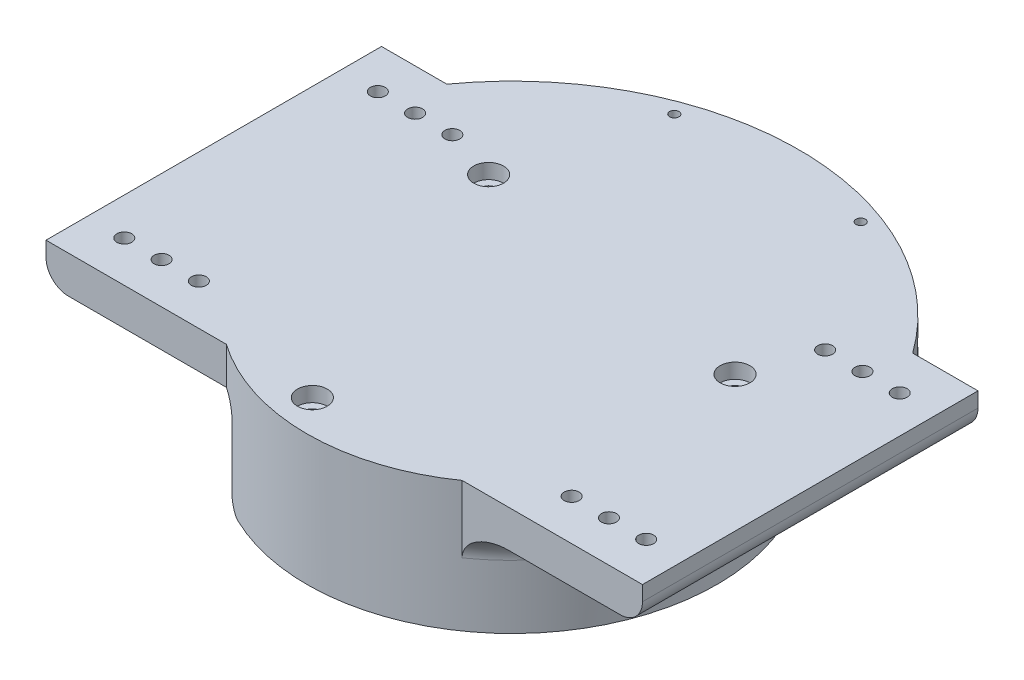
SolidWorks part; units mm, degrees
material "6061 合金"
ref_plane "前视基准面" through (0, 0, 0) normal (0, 0, 1) x (1, 0, 0)
ref_plane "上视基准面" through (0, 0, 0) normal (0, 1, 0) x (1, 0, 0)
ref_plane "右视基准面" through (0, 0, 0) normal (1, 0, 0) x (0, 0, -1)
sketch "草图1" plane through (0, 0, 0) normal (0, 1, 0) x (1, 0, 0)
  line L0 (-80, 0) -> (80, 0) construction
  line L1 (-80, 45) -> (-62.482, 45)
  line L2 (-80, 45) -> (-80, -45)
  line L3 (-80, -45) -> (-31.6228, -45)
  line L4 (80, 45) -> (80, -45)
  line L5 (-80, 45) -> (80, -45) construction
  line L6 (-80, -45) -> (80, 45) construction
  line L7 (62.482, 45) -> (80, 45)
  line L8 (43.5634, 16.2627) -> (0, 0) construction
  line L9 (-55, 0) -> (0, 0) construction
  line L10 (31.6228, -45) -> (80, -45)
  circle A5 centre (0, 0) radius 46.5 construction
  circle A9 centre (43.5634, 16.2627) radius 2
  circle A10 centre (-7.6978, -45.8584) radius 2
  circle A11 centre (-35.8657, 29.5957) radius 2
  arc A14 (-31.6228, -45) -> (31.6228, -45) centre (0, 0) ccw
  circle A15 centre (0, 0) radius 77 construction
  arc A16 (62.482, 45) -> (-62.482, 45) centre (0, 0) ccw
  dimension "D5" = 154
  dimension "D8" = 93
  dimension "D9" = 4
  dimension "D11" = 3
  dimension "D2" = 160
  dimension "D3" = 45
  dimension "D10" = 20.471
extrude "凸台-拉伸3" add sketch "草图1" along normal blind 10
sketch "草图4" plane through (0, 0, 0) normal (0, 1, 0) x (1, 0, 0)
  line L0 (-125, 0) -> (125, 0) construction
  line L5 (-125, 65) -> (125, -65) construction
  line L6 (-125, -65) -> (125, 65) construction
  line L7 (0, 0) -> (-27.5, -47.6314) construction
  line L8 (43.5634, 16.2627) -> (0, 0) construction
  line L9 (-55, 0) -> (0, 0) construction
  line L10 (-27.5, -47.6314) -> (-25, -43.3013)
  line L11 (-55, 0) -> (-50, 0)
  arc A0 (-25, -43.3013) -> (-50, 0) centre (0, 0) ccw
  circle A5 centre (0, 0) radius 46.5 construction
  arc A12 (-27.5, -47.6314) -> (-55, 0) centre (0, 0) ccw
  dimension "D1" = 100
  dimension "D4" = 110
  dimension "D5" = 60
  dimension "D8" = 93
  dimension "D10" = 20.471
extrude "凸台-拉伸4" add sketch "草图4" against normal blind 25
sketch "草图6" plane through (0, 10, 0) normal (0, 1, 0) x (1, 0, 0)
  line L0 (70, 34) -> (60, 34) construction
  line L1 (-70, 34) -> (70, 34) construction
  line L2 (-70, 34) -> (-70, -34) construction
  line L3 (-70, -34) -> (70, -34) construction
  line L4 (70, 34) -> (70, -34) construction
  line L5 (-70, 34) -> (70, -34) construction
  line L6 (-70, -34) -> (70, 34) construction
  line L7 (-70, 34) -> (-60, 34) construction
  circle A0 centre (70, -34) radius 2
  circle A1 centre (70, 34) radius 2
  circle A2 centre (60, 34) radius 2
  circle A3 centre (60, -34) radius 2
  circle A4 centre (50, 34) radius 2
  circle A5 centre (50, -34) radius 2
  circle A6 centre (-70, -34) radius 2
  circle A7 centre (-70, 34) radius 2
  circle A8 centre (-60, 34) radius 2
  circle A9 centre (-60, -34) radius 2
  circle A10 centre (-50, 34) radius 2
  circle A11 centre (-50, -34) radius 2
  point P0 (0, 0)
  dimension "D3" = 4
  dimension "D4" = 4
  dimension "D5" = 3
  dimension "D7" = 4
  dimension "D8" = 4
  dimension "D9" = 3
  dimension "D1" = 68
  dimension "D2" = 140
  dimension "D6" = 10
  dimension "D10" = 10
extrude "切除-拉伸1" cut sketch "草图6" against normal up to next
sketch "草图7" plane through (0, 10, 0) normal (0, 1, 0) x (1, 0, 0)
  circle A1 centre (43.5634, 16.2627) radius 4
  circle A2 centre (-35.8657, 29.5957) radius 4
  circle A3 centre (-7.6978, -45.8584) radius 4
  dimension "D1" = 8
  dimension "D2" = 8
  dimension "D3" = 8
extrude "切除-拉伸2" cut sketch "草图7" against normal blind 4
sketch "草图8" plane through (0, 0, 0) normal (1, 0, 0) x (0, 0, -1)
  line L0 (56, 0) -> (80.5, 0)
  line L1 (45, 0) -> (77, 0) construction
  line L2 (80.44, 3.65) -> (80.5, 0)
  line L3 (60.44, 3.65) -> (80.44, 3.65)
  line L4 (68.2725, -0.1574) -> (68.2725, 3.65) construction
  spline S1 degree 3 poles (56, 0) (55.9994, 0.3206) (56.0986, 0.8842) (56.5128, 1.818) (57.3331, 2.7114) (58.6537, 3.4247) (59.7761, 3.6508) (60.44, 3.65) knots 0.008209 0.008209 0.008209 0.008209 0.124948 0.249963 0.499993 0.750023 0.99192 0.99192 0.99192 0.99192 weights 1 1 1 1 1 1 1 1
  dimension "D1" = 24.5
  dimension "D2" = 56
  dimension "D3" = 20
extrude "切除-拉伸3" cut sketch "草图8" against normal through all both and the other way through all
sketch "草图9" plane through (0, 3.65, 0) normal (0, -1, 0) x (1, 0, 0)
  line L0 (0, 0) -> (0, -137.08) construction
  line L1 (-4.6944, -68.54) -> (16.9681, -68.54) construction
  line L2 (-47.7075, -60.44) -> (47.7075, -60.44) construction
  line L3 (-25, -68.54) -> (25, -68.54) construction
  circle A0 centre (-25, -68.54) radius 1.25
  circle A1 centre (25, -68.54) radius 1.25
  point P9 (0, -68.54)
  dimension "D3" = 2.5
  dimension "D4" = 2.5
  dimension "D1" = 8.1
  dimension "D2" = 50
extrude "切除-拉伸4" cut sketch "草图9" against normal through all
fillet "圆角1" radius 4 4 edges at (-26.25, -25, 45.4663) (-52.5, -25, 0) (-52.5, 0, 0) (-26.25, 0, 45.4663)
fillet "圆角2" radius 8 1 edges at (23.5622, 0, -49.6973)
fillet "圆角3" radius 6 2 edges at (80, 0, 0) (-80, 0, 0)
